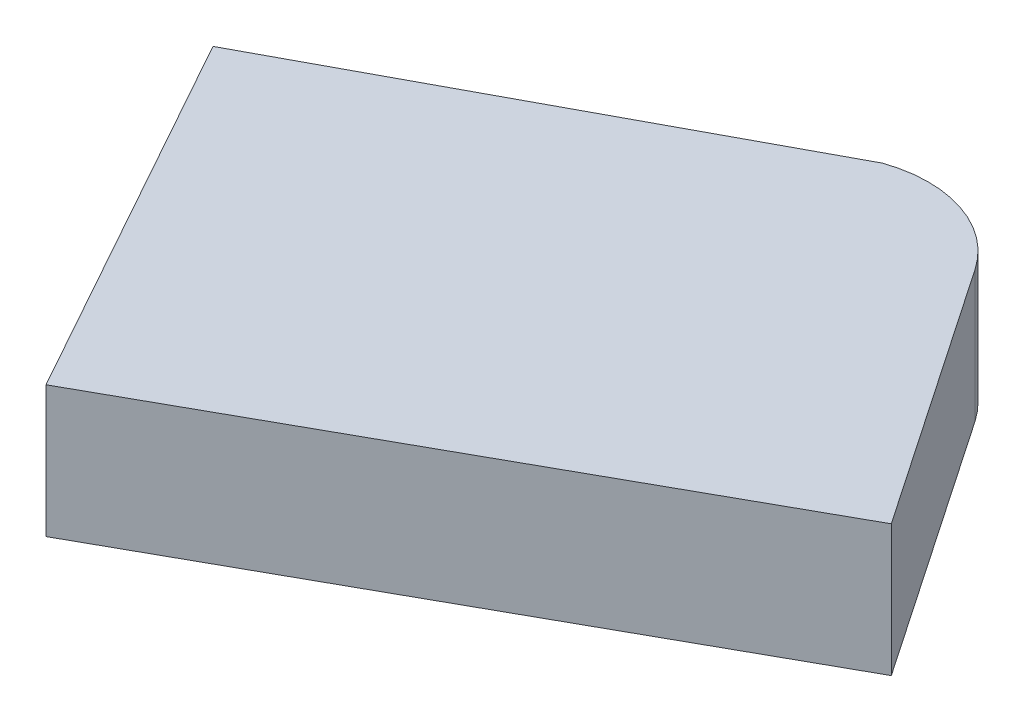
SolidWorks part; units mm, degrees
ref_plane "Front Plane" through (0, 0, 0) normal (0, 0, 1) x (1, 0, 0)
ref_plane "Top Plane" through (0, 0, 0) normal (0, 1, 0) x (1, 0, 0)
ref_plane "Right Plane" through (0, 0, 0) normal (1, 0, 0) x (0, 0, -1)
sketch "Sketch1" plane through (0, 0, 0) normal (0, 1, 0) x (1, 0, 0)
  line L0 (91.413, -1.6405) -> (53.4728, 54.1063)
  line L1 (91.413, -1.6405) -> (-23.9972, -65.8715)
  line L2 (-23.9972, -65.8715) -> (-68.5304, 14.1456)
  line L3 (24.0651, 63.7828) -> (-68.5304, 14.1456)
  line L4 (25.0871, 61.4487) -> (-65.0561, 13.1261)
  line L5 (-23.013, -62.4169) -> (-65.0561, 13.1261)
  line L6 (87.7497, -0.7724) -> (-23.013, -62.4169)
  line L7 (87.7497, -0.7724) -> (51.3729, 52.6772)
  arc A0 (53.4728, 54.1063) -> (24.0651, 63.7828) centre (32.4745, 39.8153) ccw
  arc A1 (51.3729, 52.6772) -> (25.0871, 61.4487) centre (32.4745, 39.8153) ccw
  point P12 (0, 0)
  dimension "D1" = 132.08
extrude "Boss-Extrude1" add sketch "Sketch1" along normal blind 27.94 contours L0 A0 L3 L2 L1
extrude "Cut-Extrude1" cut sketch "Sketch1<6>" along normal blind 25.4 contours L6 L5 L4 A1 L7
sketch "Sketch1<6>" plane through (0, 0, 0) normal (0, 1, 0) x (1, 0, 0) same geometry as "Sketch1"
